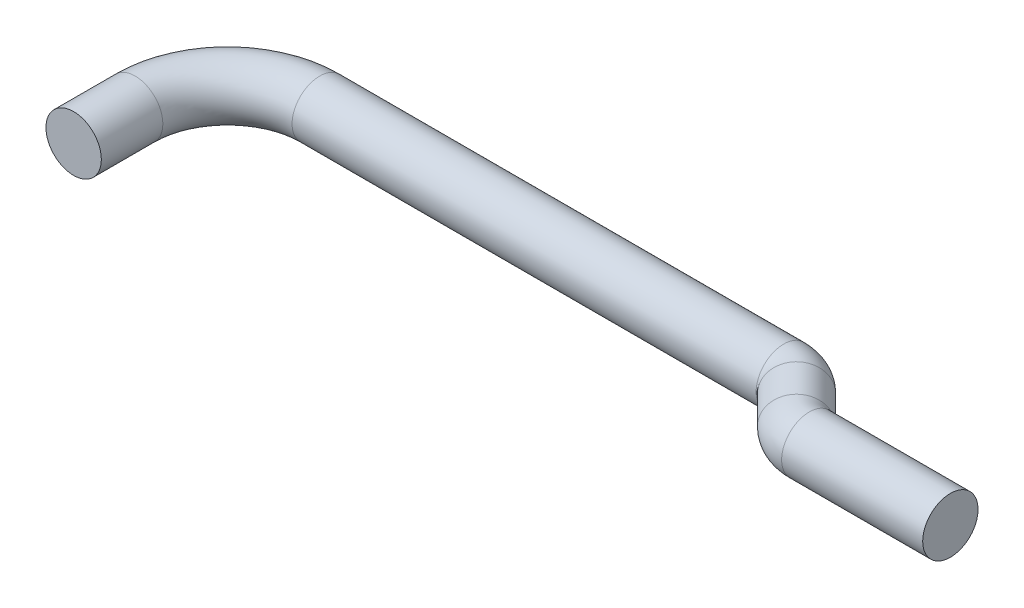
SolidWorks part; units mm, degrees
ref_plane "Front Plane" through (0, 0, 0) normal (0, 0, 1) x (1, 0, 0)
ref_plane "Top Plane" through (0, 0, 0) normal (0, 1, 0) x (1, 0, 0)
ref_plane "Right Plane" through (0, 0, 0) normal (1, 0, 0) x (0, 0, -1)
sketch "Sketch1" plane through (0, 0, 0) normal (0, 1, 0) x (1, 0, 0)
  line L1 (30, 50) -> (180.8579, 50)
  line L2 (187.9289, 47.0711) -> (197.0711, 37.9289)
  line L3 (204.1421, 35) -> (250, 35)
  line L4 (0, -55) -> (0, 55) construction
  line L5 (0, 20) -> (0, 0)
  line L6 (-55, 0) -> (55, 0) construction
  arc A0 (0, 20) -> (30, 50) centre (30, 20) cw
  arc A1 (180.8579, 50) -> (187.9289, 47.0711) centre (180.8579, 40) cw
  arc A2 (197.0711, 37.9289) -> (204.1421, 35) centre (204.1421, 45) ccw
  point P16 (200, 35)
  dimension "D1" = 250
  dimension "D4" = 30
  dimension "D7" = 10
  dimension "D2" = 50
  dimension "D3" = 15
  dimension "D5" = 50
  dimension "D6" = 45
sketch "Sketch2" plane through (0, 0, 0) normal (0, 0, 1) x (1, 0, 0)
  circle A0 centre (0, 0) radius 9
  dimension "D1" = 18
sweep "Sweep1" add profiles "Sketch2" path "Sketch1"
